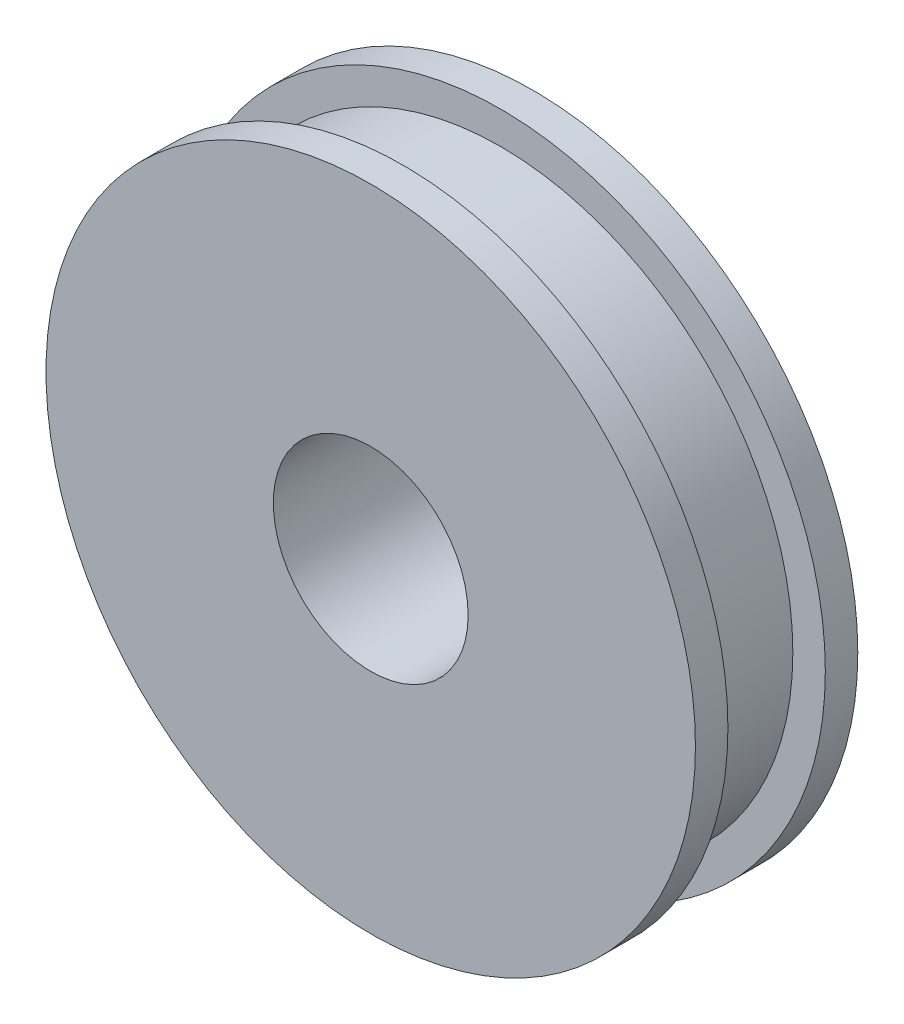
SolidWorks part; units mm, degrees
ref_plane "Front Plane" through (0, 0, 0) normal (0, 0, 1) x (1, 0, 0)
ref_plane "Top Plane" through (0, 0, 0) normal (0, 1, 0) x (1, 0, 0)
ref_plane "Right Plane" through (0, 0, 0) normal (1, 0, 0) x (0, 0, -1)
sketch "Sketch1" plane through (0, 0, 0) normal (0, 0, 1) x (1, 0, 0)
  circle A0 centre (0, 0) radius 3
  circle A1 centre (0, 0) radius 10
  circle A2 centre (0, 0) radius 9
  dimension "D1" = 6
  dimension "D2" = 20
  dimension "D3" = 18
extrude "Boss-Extrude1" add sketch "Sketch1" along normal blind 5 contours A1 A2 | A2 A0 region at (-9.7172, 0, 0) region at (-8.7454, 0, 0)
extrude "Cut-Extrude1" cut sketch "Sketch1<3>" along normal blind 3 from offset 1 contours A1 A2 region at (-9.7172, 0, 0)
sketch "Sketch1<3>" plane through (0, 0, 0) normal (0, 0, 1) x (1, 0, 0) same geometry as "Sketch1"
